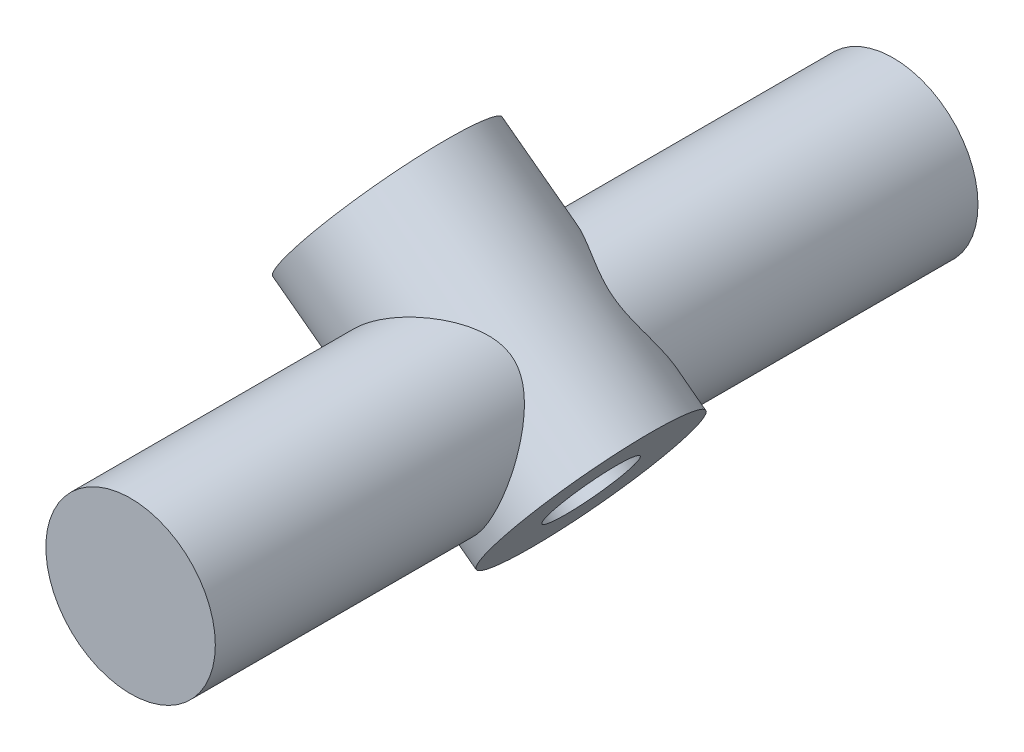
SolidWorks part; units mm, degrees
material "AISI 4130 Acero recocido a 865C"
ref_plane "Alzado" through (0, 0, 0) normal (0, 0, 1) x (1, 0, 0)
ref_plane "Planta" through (0, 0, 0) normal (0, 1, 0) x (1, 0, 0)
ref_plane "Vista lateral" through (0, 0, 0) normal (1, 0, 0) x (0, 0, -1)
sketch3d "Sk_Puente"
  line L0 (-215.7592, 344.7566, -27) -> (-215.7592, 344.7566, 27)
sweep "Puente" add path "Sk_Puente" circular profile diameter 12 parameters "D3"=12
sketch3d "Sk_Boss_tornillo"
  line L0 (-210.1546, 340.5627, 0) -> (-224.5664, 351.347, 0)
  dimension "D1" = 18
sweep "Boss_tornillo" add path "Sk_Boss_tornillo" circular profile diameter 14 parameters "D3"=14
sketch3d "Sk_Taladro_tornillo"
  line L0 (-209.3539, 339.9636, 0) -> (-225.367, 351.9461, 0)
  dimension "D1" = 20
sweep "Taladro_tornillo" cut path "Sk_Taladro_tornillo" circular profile diameter 6 parameters "D3"=6
